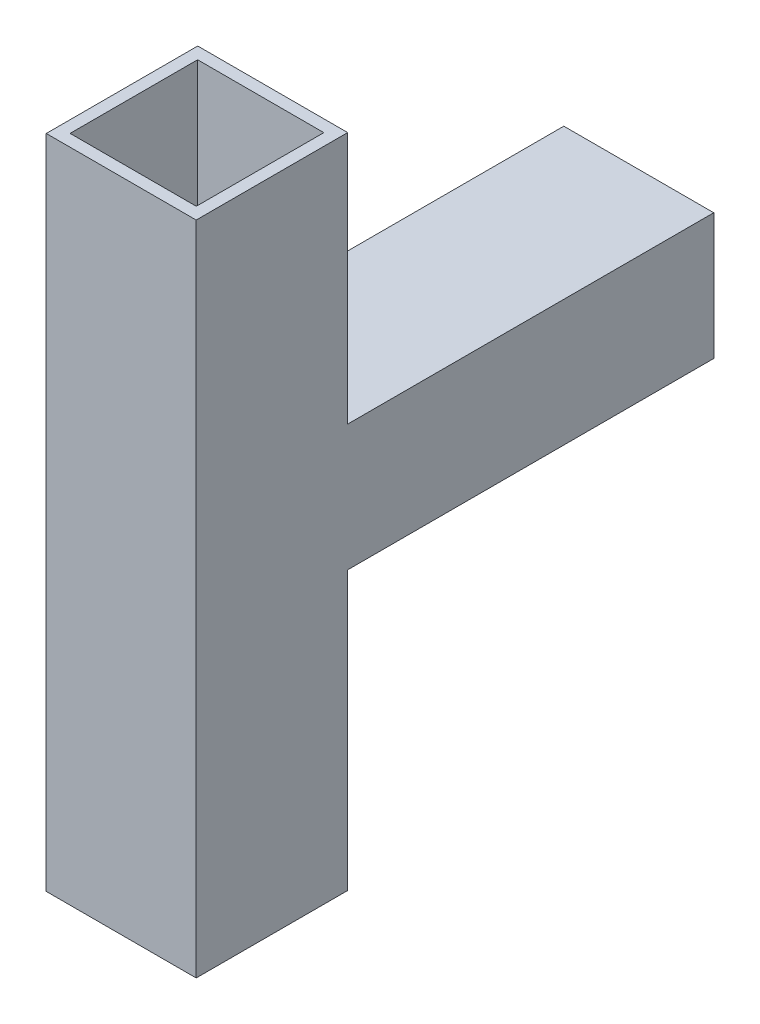
SolidWorks part; units mm, degrees
ref_plane "Front Plane" through (0, 0, 0) normal (0, 0, 1) x (1, 0, 0)
ref_plane "Top Plane" through (0, 0, 0) normal (0, 1, 0) x (1, 0, 0)
ref_plane "Right Plane" through (0, 0, 0) normal (1, 0, 0) x (0, 0, -1)
sketch "Sketch1" plane through (0, 0, 0) normal (0, 1, 0) x (1, 0, 0)
  line L1 (-2.9694, -3) -> (2.9694, -3)
  line L2 (-2.9694, -3) -> (-2.9694, 3)
  line L3 (-2.9694, 3) -> (2.9694, 3)
  line L4 (2.9694, -3) -> (2.9694, 3)
  line L5 (-2.9694, -3) -> (2.9694, 3) construction
  line L6 (-2.9694, 3) -> (2.9694, -3) construction
  line L7 (-2.5, -2.5258) -> (2.5, -2.5258)
  line L8 (-2.5, -2.5258) -> (-2.5, 2.5258)
  line L9 (-2.5, 2.5258) -> (2.5, 2.5258)
  line L10 (2.5, -2.5258) -> (2.5, 2.5258)
  line L11 (-2.5, -2.5258) -> (2.5, 2.5258) construction
  line L12 (-2.5, 2.5258) -> (2.5, -2.5258) construction
  point P0 (0, 0)
  point P6 (0, 0)
  dimension "D1" = 6
  dimension "D2" = 5
extrude "Boss-Extrude1" add sketch "Sketch1" along normal blind 26
sketch "Sketch4" plane through (0, 0, -3) normal (0, 0, -1) x (-1, 0, 0)
  line L0 (-2.9694, 26) -> (-2.9694, 0) construction
  line L1 (-2.9694, 11) -> (2.9694, 11)
  line L2 (-2.9694, 11) -> (-2.9694, 16)
  line L3 (-2.9694, 16) -> (2.9694, 16)
  line L4 (2.9694, 11) -> (2.9694, 16)
  line L5 (2.9694, 26) -> (2.9694, 0) construction
  line L6 (-2.9694, 26) -> (2.9694, 26) construction
  dimension "D1" = 5
  dimension "D2" = 10
extrude "Boss-Extrude2" add sketch "Sketch4" along normal blind 14.5
sketch "Sketch5" plane through (0, 0, -17.5) normal (0, 0, -1) x (-1, 0, 0)
  line L0 (-2.9694, 11) -> (2.9694, 11) construction
  line L1 (-1.9694, 11.5) -> (2.0306, 11.5)
  line L2 (-1.9694, 11.5) -> (-1.9694, 15.5)
  line L3 (-1.9694, 15.5) -> (2.0306, 15.5)
  line L4 (2.0306, 11.5) -> (2.0306, 15.5)
  line L5 (-1.9694, 11.5) -> (2.0306, 15.5) construction
  line L6 (-1.9694, 15.5) -> (2.0306, 11.5) construction
  line L7 (-2.9694, 16) -> (-2.9694, 11) construction
  point P0 (0.0306, 13.5)
  dimension "D1" = 4
  dimension "D2" = 4
  dimension "D3" = 0.5
  dimension "D4" = 1
extrude "Cut-Extrude1" cut sketch "Sketch5" against normal up to surface (14.9742 mm away) up to face at (0, 13, -2.5258)
scale "Scale1" scale about centroid uniform scaling yes scale factor 6
